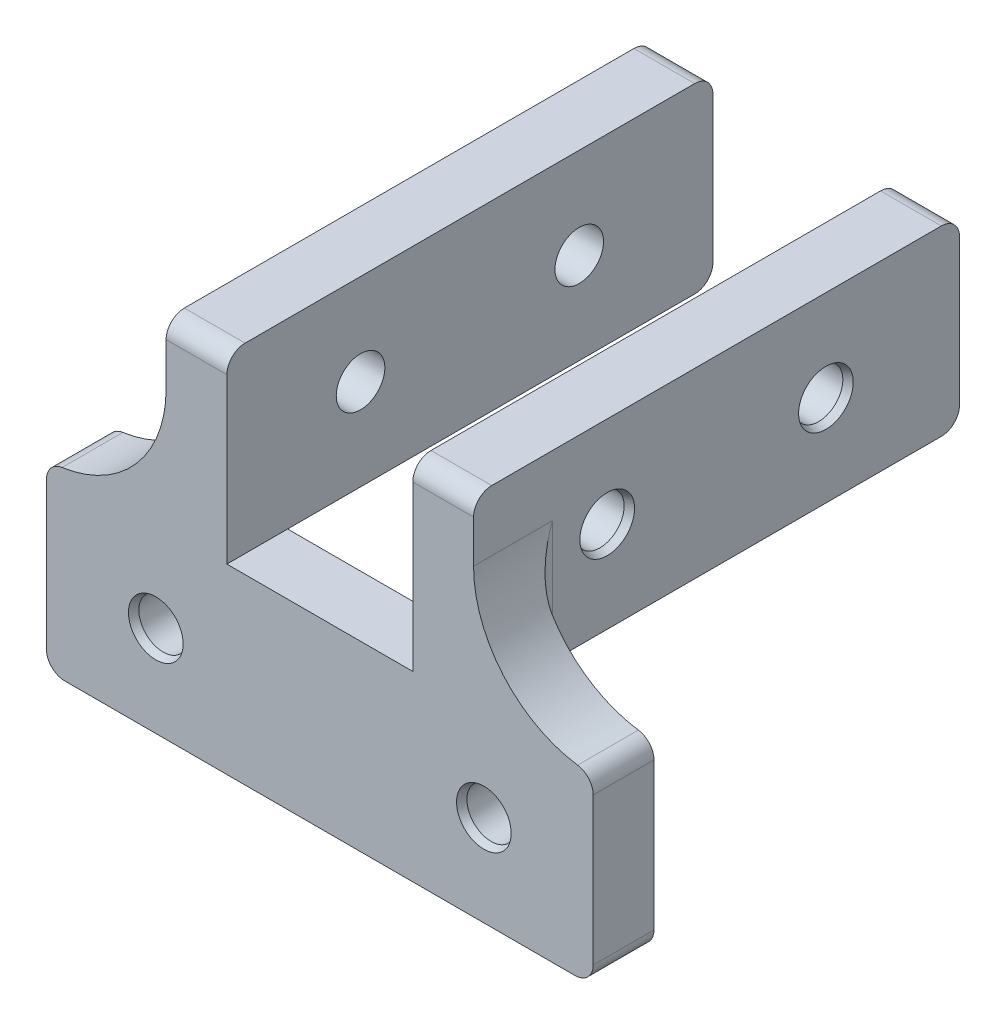
SolidWorks part; units mm, degrees
ref_plane "Front Plane" through (0, 0, 0) normal (0, 0, 1) x (1, 0, 0)
ref_plane "Top Plane" through (0, 0, 0) normal (0, 1, 0) x (1, 0, 0)
ref_plane "Right Plane" through (0, 0, 0) normal (1, 0, 0) x (0, 0, -1)
sketch "Sketch1" plane through (0, 0, 0) normal (0, 0, 1) x (1, 0, 0)
  line L1 (-22.5, -7.5) -> (22.5, -7.5)
  line L2 (-22.5, -7.5) -> (-22.5, 7.5)
  line L3 (-22.5, 7.5) -> (22.5, 7.5)
  line L4 (22.5, -7.5) -> (22.5, 7.5)
  line L5 (-22.5, -7.5) -> (22.5, 7.5) construction
  line L6 (-22.5, 7.5) -> (22.5, -7.5) construction
  point P0 (0, 0)
  dimension "D1" = 15
  dimension "D2" = 45
extrude "Boss-Extrude1" add sketch "Sketch1" along normal blind 5
sketch "Sketch3" plane through (0, 7.5, 0) normal (0, 1, 0) x (1, 0, 0)
  line L0 (-7.65, 0) -> (7.65, 0) construction
  line L1 (22.5, 0) -> (-22.5, 0) construction
  line L2 (-7.65, 0) -> (-7.65, -5)
  line L3 (22.5, -5) -> (-22.5, -5) construction
  line L4 (-7.65, -5) -> (-12.65, -5)
  line L5 (-12.65, -5) -> (-12.65, 35)
  line L6 (-12.65, 35) -> (-7.65, 35)
  line L7 (-7.65, 35) -> (-7.65, 0)
  line L8 (0, 0) -> (0, -5) construction
  line L9 (7.65, -5) -> (12.65, -5)
  line L10 (7.65, 0) -> (7.65, -5)
  line L11 (12.65, -5) -> (12.65, 35)
  line L12 (7.65, 35) -> (7.65, 0)
  line L13 (12.65, 35) -> (7.65, 35)
  point P6 (0, 0)
  dimension "D1" = 15.3
  dimension "D2" = 5
  dimension "D3" = 40
extrude "Boss-Extrude2" add sketch "Sketch3" along normal blind 15
sketch "Sketch5" plane through (-12.65, 0, 0) normal (-1, 0, 0) x (0, 0, 1)
  line L3 (5, 15) -> (-6, 15) construction
  line L4 (5, 22.5) -> (5, 7.5) construction
  line L5 (-35, 15) -> (-24, 15) construction
  line L6 (-35, 22.5) -> (-35, 7.5) construction
  point P1 (-6, 15)
  point P5 (-24, 15)
  dimension "D1" = 11
hole_wizard "Ø4.0 (4) Diameter Hole1" positions "Sketch5" profile "Sketch8" hole size "Ø4.0" standard "ANSI Metric" end condition up to next
sketch "Sketch8" plane through (-12.65, 15, -24) normal (0, 1, 0) x (0, 0, 1)
  line L0 (0, 0) -> (0, 5)
  line L1 (0, 5) -> (2, 5)
  line L2 (2, 5) -> (2, 0.6036)
  line L3 (2, 0.6036) -> (2.25, 0)
  line L5 (2.25, 0) -> (0, 0)
  line L6 (-2, 0.6036) -> (-2.25, 0) construction
  line L11 (0, -6.35) -> (0, 107.95) construction
  dimension "Thru Hole Dia." = 4
  dimension "Thru Hole Depth" = 5
  dimension "Near C'Sink Dia." = 4.5
  dimension "Near C'Sink Angle" = 45
mirror "Mirror3" about plane through (0, 0, 0) normal (1, 0, 0) of "Ø4.0 (4) Diameter Hole1"
sketch "Sketch11" plane through (0, 0, 5) normal (0, 0, 1) x (1, 0, 0)
  line L0 (-22.5, 0) -> (-13.5, 0) construction
  line L1 (-22.5, 7.5) -> (-22.5, -7.5) construction
  line L2 (22.5, 0) -> (13.5, 0) construction
  line L3 (22.5, -7.5) -> (22.5, 7.5) construction
  point P1 (-13.5, 0)
  point P6 (13.5, 0)
  dimension "D1" = 9
hole_wizard "Ø4.0 (4) Diameter Hole2" positions "Sketch11" profile "Sketch12" hole size "Ø4.0" standard "ANSI Metric" end condition up to next
sketch "Sketch12" plane through (13.5, 0, 5) normal (1, 0, 0) x (0, -1, 0)
  line L0 (0, 0) -> (0, 5)
  line L1 (0, 5) -> (2, 5)
  line L2 (2, 5) -> (2, 0.6036)
  line L3 (2, 0.6036) -> (2.25, 0)
  line L5 (2.25, 0) -> (0, 0)
  line L6 (-2, 0.6036) -> (-2.25, 0) construction
  line L11 (0, -6.35) -> (0, 107.95) construction
  dimension "Thru Hole Dia." = 4
  dimension "Thru Hole Depth" = 5
  dimension "Near C'Sink Dia." = 4.5
  dimension "Near C'Sink Angle" = 45
fillet "Fillet1" radius 10 2 edges at (12.65, 7.5, 2.5) (-12.65, 7.5, 2.5)
fillet "Fillet2" radius 1.5 12 edges at (12.65, 12.4994, 0) (-10.15, 7.5, -35) (-12.65, 12.4994, 0) (10.15, 7.5, -35) (10.15, 22.5, 5) (10.15, 22.5, -35) (-10.15, 22.5, 5) (-10.15, 22.5, -35) (22.5, -7.5, 2.5) (-22.5, -7.5, 2.5) (22.5, 7.5, 2.5) (-22.5, 7.5, 2.5)
